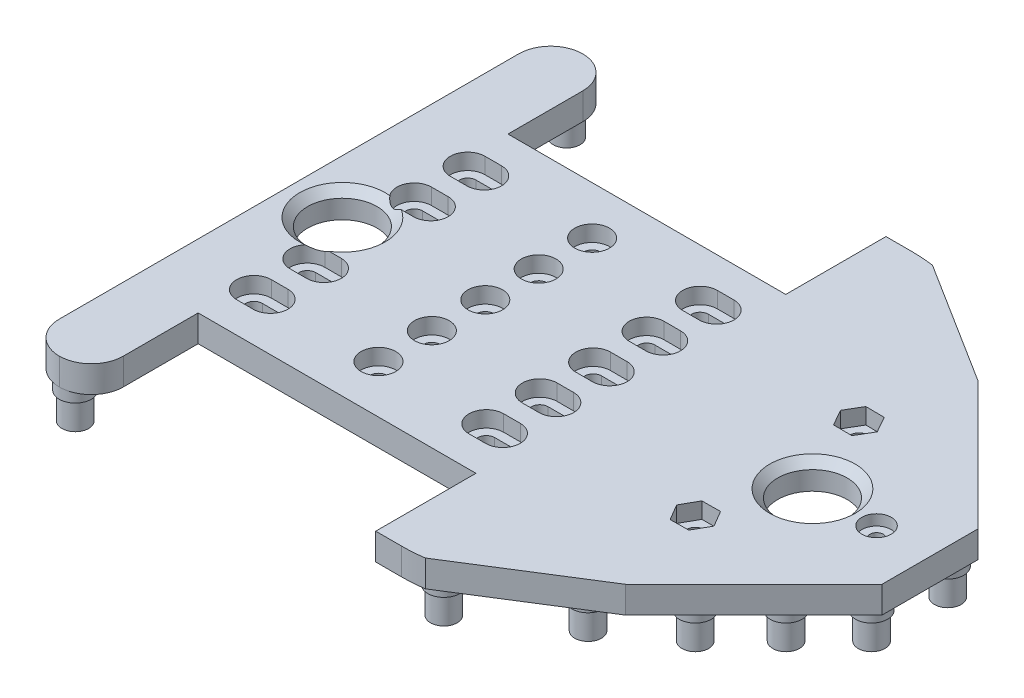
SolidWorks part; units mm, degrees
ref_plane "Front Plane" through (0, 0, 0) normal (0, 0, 1) x (1, 0, 0)
ref_plane "Top Plane" through (0, 0, 0) normal (0, 1, 0) x (1, 0, 0)
ref_plane "Right Plane" through (0, 0, 0) normal (1, 0, 0) x (0, 0, -1)
sketch "Sketch1" plane through (0, 0, 0) normal (0, 1, 0) x (1, 0, 0)
  line L6 (70.2134, 28.8107) -> (31.4419, 67.5821)
  line L47 (70.2134, 19.8215) -> (-33.2366, 19.8215) construction
  line L51 (14.2134, -9.1785) -> (-37.7866, -9.1785)
  line L52 (-37.7866, -9.1785) -> (-37.7866, -29.1785)
  line L53 (-37.7866, -29.1785) -> (-49.7866, -29.1785)
  line L54 (-49.7866, -29.1785) -> (-49.7866, 68.8215)
  line L55 (-49.7866, 68.8215) -> (-37.7866, 68.8215)
  line L56 (-37.7866, 68.8215) -> (-37.7866, 48.8215)
  line L57 (-37.7866, 48.8215) -> (14.2134, 48.8215)
  line L67 (14.2134, 48.8215) -> (14.2134, 67.5821)
  line L68 (14.2134, 67.5821) -> (31.4419, 67.5821)
  line L70 (14.2134, -9.1785) -> (14.2134, -27.9391)
  line L71 (70.2134, 28.8107) -> (70.2134, 10.8324)
  line L72 (14.2134, -27.9391) -> (31.4419, -27.9391)
  line L73 (70.2134, 10.8324) -> (31.4419, -27.9391)
  line L74 (31.4419, 67.5821) -> (31.4419, -27.9391) construction
  line L75 (-36.3366, 39.8215) -> (-33.2366, 39.8215) construction
  line L76 (-36.3366, 41.3715) -> (-33.2366, 41.3715)
  line L77 (-36.3366, 38.2715) -> (-33.2366, 38.2715)
  line L78 (7.1634, 39.8215) -> (10.2634, 39.8215) construction
  line L81 (7.1634, 41.3715) -> (10.2634, 41.3715)
  line L84 (7.1634, 38.2715) -> (10.2634, 38.2715)
  line L87 (7.1634, 29.8215) -> (10.2634, 29.8215) construction
  line L90 (7.1634, 31.3715) -> (10.2634, 31.3715)
  line L93 (7.1634, 28.2715) -> (10.2634, 28.2715)
  line L96 (7.1634, 19.8215) -> (10.2634, 19.8215) construction
  line L99 (7.1634, 21.3715) -> (10.2634, 21.3715)
  line L102 (7.1634, 18.2715) -> (10.2634, 18.2715)
  line L105 (7.1634, 9.8215) -> (10.2634, 9.8215) construction
  line L106 (7.1634, 11.3715) -> (10.2634, 11.3715)
  line L107 (7.1634, 8.2715) -> (10.2634, 8.2715)
  line L108 (7.1634, -0.1785) -> (10.2634, -0.1785) construction
  line L109 (7.1634, 1.3715) -> (10.2634, 1.3715)
  line L110 (7.1634, -1.7285) -> (10.2634, -1.7285)
  line L111 (-36.3366, 29.8215) -> (-33.2366, 29.8215) construction
  line L112 (-36.3366, 31.3715) -> (-33.2366, 31.3715)
  line L113 (-36.3366, 28.2715) -> (-33.2366, 28.2715)
  line L114 (-36.3366, 19.8215) -> (-33.2366, 19.8215) construction
  line L117 (-36.3366, 9.8215) -> (-33.2366, 9.8215) construction
  line L118 (-36.3366, 11.3715) -> (-33.2366, 11.3715)
  line L119 (-36.3366, 8.2715) -> (-33.2366, 8.2715)
  line L120 (-36.3366, -0.1785) -> (-33.2366, -0.1785) construction
  line L121 (-36.3366, 1.3715) -> (-33.2366, 1.3715)
  line L122 (-36.3366, -1.7285) -> (-33.2366, -1.7285)
  line L123 (-34.7866, -0.1785) -> (8.7134, -0.1785) construction
  line L127 (-33.2366, 19.8215) -> (-49.7866, 19.8215) construction
  line L158 (-36.3366, 19.8215) -> (-33.2366, 19.8215) construction
  line L159 (-36.3366, 21.3715) -> (-33.2366, 21.3715) [skipped]
  line L160 (-36.3366, 18.2715) -> (-33.2366, 18.2715) [skipped]
  line L161 (-36.3366, 19.8215) -> (-33.2366, 19.8215) construction
  line L162 (-36.3366, 21.3715) -> (-33.2366, 21.3715) [skipped]
  line L163 (-36.3366, 18.2715) -> (-33.2366, 18.2715) [skipped]
  circle A26 centre (48.2134, 19.8215) radius 6.5
  circle A27 centre (-34.7866, 39.8215) radius 1.55 construction
  arc A44 (-36.3366, 41.3715) -> (-36.3366, 38.2715) centre (-36.3366, 39.8215) ccw
  arc A45 (-33.2366, 38.2715) -> (-33.2366, 41.3715) centre (-33.2366, 39.8215) ccw
  arc A64 (7.1634, 41.3715) -> (7.1634, 38.2715) centre (7.1634, 39.8215) ccw
  arc A65 (10.2634, 38.2715) -> (10.2634, 41.3715) centre (10.2634, 39.8215) ccw
  arc A66 (7.1634, 31.3715) -> (7.1634, 28.2715) centre (7.1634, 29.8215) ccw
  arc A67 (10.2634, 28.2715) -> (10.2634, 31.3715) centre (10.2634, 29.8215) ccw
  arc A68 (7.1634, 21.3715) -> (7.1634, 18.2715) centre (7.1634, 19.8215) ccw
  arc A69 (10.2634, 18.2715) -> (10.2634, 21.3715) centre (10.2634, 19.8215) ccw
  arc A70 (7.1634, 11.3715) -> (7.1634, 8.2715) centre (7.1634, 9.8215) ccw
  arc A71 (10.2634, 8.2715) -> (10.2634, 11.3715) centre (10.2634, 9.8215) ccw
  arc A72 (7.1634, 1.3715) -> (7.1634, -1.7285) centre (7.1634, -0.1785) ccw
  arc A73 (10.2634, -1.7285) -> (10.2634, 1.3715) centre (10.2634, -0.1785) ccw
  arc A74 (-36.3366, 31.3715) -> (-36.3366, 28.2715) centre (-36.3366, 29.8215) ccw
  arc A75 (-33.2366, 28.2715) -> (-33.2366, 31.3715) centre (-33.2366, 29.8215) ccw
  arc A78 (-36.3366, 11.3715) -> (-36.3366, 8.2715) centre (-36.3366, 9.8215) ccw
  arc A79 (-33.2366, 8.2715) -> (-33.2366, 11.3715) centre (-33.2366, 9.8215) ccw
  arc A80 (-36.3366, 1.3715) -> (-36.3366, -1.7285) centre (-36.3366, -0.1785) ccw
  arc A81 (-33.2366, -1.7285) -> (-33.2366, 1.3715) centre (-33.2366, -0.1785) ccw
  circle A82 centre (-13.0366, -0.1785) radius 1.55
  circle A83 centre (-13.0366, 9.8215) radius 1.55
  circle A84 centre (-13.0366, 19.8215) radius 1.55
  circle A85 centre (-13.0366, 29.8215) radius 1.55
  circle A86 centre (-13.0366, 39.8215) radius 1.55
  circle A87 centre (41.5953, 35.1284) radius 1.55
  circle A88 centre (41.5953, 4.5146) radius 1.55
  circle A89 centre (-39.7866, 19.8215) radius 6.5
  circle A91 centre (60.2134, 19.8215) radius 1.25
  arc A114 (-36.3366, 21.3715) -> (-36.3366, 18.2715) centre (-36.3366, 19.8215) ccw [skipped]
  arc A115 (-33.2366, 18.2715) -> (-33.2366, 21.3715) centre (-33.2366, 19.8215) ccw [skipped]
  point P19 (-34.7866, 39.8215)
  point P28 (8.7134, 39.8215)
  point P35 (8.7134, 29.8215)
  point P43 (8.7134, 19.8215)
  point P50 (8.7134, 9.8215)
  point P57 (8.7134, -0.1785)
  point P64 (-34.7866, 29.8215)
  point P71 (-34.7866, 19.8215)
  point P80 (-34.7866, 9.8215)
  point P88 (-34.7866, -0.1785)
  point P110 (-34.7866, 19.8215)
  point P122 (-34.7866, 19.8215)
  point P129 (-34.7866, 19.8215)
  point P136 (-34.7866, 19.8215)
  point P143 (-34.7866, 19.8215)
  point P150 (-34.7866, 19.8215)
  point P157 (-34.7866, 19.8215)
  point P164 (-34.7866, 19.8215)
  point P171 (-34.7866, 19.8215)
  point P178 (-34.7866, 19.8215)
  point P185 (-34.7866, 19.8215)
  point P192 (-34.7866, 19.8215)
  point P199 (-34.7866, 19.8215)
  dimension "D11" = 20
  dimension "D10" = 20
  dimension "D15" = 13
  dimension "D8" = 135
  dimension "D9" = 12
  dimension "D17" = 1.55
  dimension "D13" = 3.1
  dimension "D14" = 15
  dimension "D16" = 9
  dimension "D18" = 5
  dimension "D19" = 3.1
  dimension "D20" = 5
  dimension "D21" = 3.1
  dimension "D24" = 13
  dimension "D26" = 2.5
  dimension "D2" = 58
  dimension "D3" = 17.9783
  dimension "D4" = 64
  dimension "D5" = 120
  dimension "D6" = 22
  dimension "D7" = 12
  dimension "D25" = 10
  dimension "D27" = 10
  dimension "D28" = 17.2286
  dimension "D12" = 18.7606
extrude "Boss-Extrude1" add sketch "Sketch1" along normal blind 5
fillet "Fillet1" radius 30 2 edges at (31.4419, 2.5, 27.9391) (31.4419, 2.5, -67.5821)
fillet "Fillet2" radius 6 4 edges at (-37.7866, 2.5, 29.1785) (-49.7866, 2.5, 29.1785) (-37.7866, 2.5, -68.8215) (-49.7866, 2.5, -68.8215)
sketch "Sketch3" plane through (0, 5, 0) normal (0, 1, 0) x (1, 0, 0)
  line L0 (-33.2366, 39.8215) -> (-36.3366, 39.8215) construction
  line L1 (-33.2366, 36.5715) -> (-36.3366, 36.5715)
  line L2 (-33.2366, 43.0715) -> (-36.3366, 43.0715)
  line L3 (10.2634, 39.8215) -> (7.1634, 39.8215) construction
  line L4 (10.2634, 36.5715) -> (7.1634, 36.5715)
  line L5 (10.2634, 43.0715) -> (7.1634, 43.0715)
  line L6 (10.2634, 29.8215) -> (7.1634, 29.8215) construction
  line L7 (10.2634, 26.5715) -> (7.1634, 26.5715)
  line L8 (10.2634, 33.0715) -> (7.1634, 33.0715)
  line L9 (10.2634, 19.8215) -> (7.1634, 19.8215) construction
  line L10 (10.2634, 16.5715) -> (7.1634, 16.5715)
  line L11 (10.2634, 23.0715) -> (7.1634, 23.0715)
  line L12 (10.2634, 9.8215) -> (7.1634, 9.8215) construction
  line L13 (10.2634, 6.5715) -> (7.1634, 6.5715)
  line L14 (10.2634, 13.0715) -> (7.1634, 13.0715)
  line L15 (10.2634, -0.1785) -> (7.1634, -0.1785) construction
  line L16 (10.2634, -3.4285) -> (7.1634, -3.4285)
  line L17 (10.2634, 3.0715) -> (7.1634, 3.0715)
  line L18 (-33.2366, 29.8215) -> (-36.3366, 29.8215) construction
  line L19 (-33.2366, 26.5715) -> (-36.3366, 26.5715)
  line L20 (-33.2366, 33.0715) -> (-36.3366, 33.0715)
  line L21 (70.2134, 19.8215) -> (39.7181, 19.8215) construction
  line L24 (-33.2366, 9.8215) -> (-36.3366, 9.8215) construction
  line L25 (-33.2366, 6.5715) -> (-36.3366, 6.5715)
  line L26 (-33.2366, 13.0715) -> (-36.3366, 13.0715)
  line L27 (-33.2366, -0.1785) -> (-36.3366, -0.1785) construction
  line L28 (-33.2366, -3.4285) -> (-36.3366, -3.4285)
  line L29 (-33.2366, 3.0715) -> (-36.3366, 3.0715)
  line L31 (43.3551, 38.1122) -> (39.8912, 38.1443)
  line L32 (39.8912, 38.1443) -> (38.1313, 35.1606)
  line L33 (38.1313, 35.1606) -> (39.8354, 32.1446)
  line L34 (39.8354, 32.1446) -> (43.2994, 32.1124)
  line L35 (43.2994, 32.1124) -> (45.0592, 35.0962)
  line L36 (45.0592, 35.0962) -> (43.3551, 38.1122)
  line L42 (70.2134, 28.8107) -> (70.2134, 10.8324) construction
  line L43 (45.0592, 4.5468) -> (43.3551, 1.5309)
  line L44 (43.2994, 7.5306) -> (45.0592, 4.5468)
  line L45 (39.8354, 7.4984) -> (43.2994, 7.5306)
  line L46 (38.1313, 4.4825) -> (39.8354, 7.4984)
  line L47 (39.8912, 1.4987) -> (38.1313, 4.4825)
  line L48 (43.3551, 1.5309) -> (39.8912, 1.4987)
  line L87 (-33.2366, 19.8215) -> (-36.3366, 19.8215) construction
  line L88 (-33.2366, 16.5715) -> (-36.3366, 16.5715) [skipped]
  line L89 (-33.2366, 23.0715) -> (-36.3366, 23.0715) [skipped]
  line L90 (-33.2366, 19.8215) -> (-36.3366, 19.8215) construction
  line L91 (-33.2366, 16.5715) -> (-36.3366, 16.5715) [skipped]
  line L92 (-33.2366, 23.0715) -> (-36.3366, 23.0715) [skipped]
  arc A0 (-33.2366, 36.5715) -> (-33.2366, 43.0715) centre (-33.2366, 39.8215) ccw
  arc A1 (-36.3366, 43.0715) -> (-36.3366, 36.5715) centre (-36.3366, 39.8215) ccw
  arc A2 (10.2634, 36.5715) -> (10.2634, 43.0715) centre (10.2634, 39.8215) ccw
  arc A3 (7.1634, 43.0715) -> (7.1634, 36.5715) centre (7.1634, 39.8215) ccw
  arc A4 (10.2634, 26.5715) -> (10.2634, 33.0715) centre (10.2634, 29.8215) ccw
  arc A5 (7.1634, 33.0715) -> (7.1634, 26.5715) centre (7.1634, 29.8215) ccw
  arc A6 (10.2634, 16.5715) -> (10.2634, 23.0715) centre (10.2634, 19.8215) ccw
  arc A7 (7.1634, 23.0715) -> (7.1634, 16.5715) centre (7.1634, 19.8215) ccw
  arc A8 (10.2634, 6.5715) -> (10.2634, 13.0715) centre (10.2634, 9.8215) ccw
  arc A9 (7.1634, 13.0715) -> (7.1634, 6.5715) centre (7.1634, 9.8215) ccw
  arc A10 (10.2634, -3.4285) -> (10.2634, 3.0715) centre (10.2634, -0.1785) ccw
  arc A11 (7.1634, 3.0715) -> (7.1634, -3.4285) centre (7.1634, -0.1785) ccw
  arc A12 (-33.2366, 26.5715) -> (-33.2366, 33.0715) centre (-33.2366, 29.8215) ccw
  arc A13 (-36.3366, 33.0715) -> (-36.3366, 26.5715) centre (-36.3366, 29.8215) ccw
  arc A16 (-33.2366, 6.5715) -> (-33.2366, 13.0715) centre (-33.2366, 9.8215) ccw
  arc A17 (-36.3366, 13.0715) -> (-36.3366, 6.5715) centre (-36.3366, 9.8215) ccw
  arc A18 (-33.2366, -3.4285) -> (-33.2366, 3.0715) centre (-33.2366, -0.1785) ccw
  arc A19 (-36.3366, 3.0715) -> (-36.3366, -3.4285) centre (-36.3366, -0.1785) ccw
  circle A20 centre (-13.0366, 39.8215) radius 3.25
  circle A21 centre (-13.0366, 29.8215) radius 3.25
  circle A22 centre (-13.0366, 19.8215) radius 3.25
  circle A23 centre (-13.0366, 9.8215) radius 3.25
  circle A24 centre (-13.0366, -0.1785) radius 3.25
  circle A27 centre (41.5953, 35.1284) radius 3 construction
  arc A60 (-33.2366, 16.5715) -> (-33.2366, 23.0715) centre (-33.2366, 19.8215) ccw [skipped]
  arc A61 (-36.3366, 23.0715) -> (-36.3366, 16.5715) centre (-36.3366, 19.8215) ccw [skipped]
  point P4 (-34.7866, 39.8215)
  point P14 (8.7134, 39.8215)
  point P21 (8.7134, 29.8215)
  point P28 (8.7134, 19.8215)
  point P35 (8.7134, 9.8215)
  point P42 (8.7134, -0.1785)
  point P49 (-34.7866, 29.8215)
  point P63 (-34.7866, 9.8215)
  point P70 (-34.7866, -0.1785)
  point P101 (-34.7866, 19.8215)
  point P108 (-34.7866, 19.8215)
  point P115 (-34.7866, 19.8215)
  point P122 (-34.7866, 19.8215)
  point P129 (-34.7866, 19.8215)
  point P136 (-34.7866, 19.8215)
  point P143 (-34.7866, 19.8215)
  point P150 (-34.7866, 19.8215)
  point P157 (-34.7866, 19.8215)
  point P164 (-34.7866, 19.8215)
  point P171 (-34.7866, 19.8215)
  point P178 (-34.7866, 19.8215)
  point P185 (-34.7866, 19.8215)
  point P192 (-34.7866, 19.8215)
  point P199 (-34.7866, 19.8215)
  point P206 (-34.7866, 19.8215)
  point P213 (-34.7866, 19.8215)
  dimension "D1" = 3.25
  dimension "D3" = 6.5
  dimension "D5" = 6
  dimension "D6" = 6
  dimension "D2" = 5
  dimension "D4" = 5
extrude "Cut-Extrude2" cut sketch "Sketch3" against normal blind 3
sketch "Sketch4" plane through (0, 0, 0) normal (0, -1, 0) x (-1, 0, 0)
  line L0 (-70.2134, 19.8215) -> (49.7866, 19.8215) construction
  line L1 (-70.2134, 28.8107) -> (-70.2134, 10.8324) construction
  line L2 (49.7866, -23.1785) -> (49.7866, 62.8215) construction
  line L3 (-14.2134, -9.1785) -> (-14.2134, -27.9391) construction
  line L4 (-14.2134, -9.1785) -> (37.7866, -9.1785) construction
  line L5 (43.7866, -29.1785) -> (43.7866, 68.8215) construction
  line L7 (-70.2134, 10.8324) -> (-40.2287, -19.1523) construction
  circle A0 centre (-22.2134, -23.1785) radius 3
  circle A1 centre (-38.2134, -12.1785) radius 3
  circle A2 centre (-22.2134, -23.1785) radius 8 construction
  circle A3 centre (-38.2134, -12.1785) radius 8 construction
  circle A4 centre (-49.9134, 43.4538) radius 5 construction
  circle A5 centre (-66.4134, 26.9538) radius 5 construction
  circle A8 centre (43.7866, -26.1785) radius 3
  circle A9 centre (43.7866, -26.1785) radius 5 construction
  circle A10 centre (43.7866, 65.8215) radius 5 construction
  circle A11 centre (43.7866, 65.8215) radius 3
  circle A18 centre (-58.4134, 34.9538) radius 5 construction
  circle A19 centre (-38.2134, 51.8215) radius 8 construction
  circle A20 centre (-22.2134, 62.8215) radius 8 construction
  circle A24 centre (-58.4134, 4.6892) radius 5 construction
  circle A25 centre (-58.4134, 4.6892) radius 3
  circle A26 centre (-49.9134, -3.8108) radius 3
  circle A27 centre (-66.4134, 12.6892) radius 3
  circle A28 centre (-66.4134, 12.6892) radius 5 construction
  circle A29 centre (-49.9134, -3.8108) radius 5 construction
  circle A30 centre (-66.4134, 26.9538) radius 3
  circle A31 centre (-49.9134, 43.4538) radius 3
  circle A32 centre (-58.4134, 34.9538) radius 3
  circle A33 centre (-38.2134, 51.8215) radius 3
  circle A34 centre (-22.2134, 62.8215) radius 3
  dimension "D1" = 6
  dimension "D2" = 8
  dimension "D4" = 16
  dimension "D5" = 24
  dimension "D6" = 3
  dimension "D7" = 6
  dimension "D8" = 6
  dimension "D9" = 10
  dimension "D11" = 10
  dimension "D16" = 6
  dimension "D17" = 6
  dimension "D18" = 4
  dimension "D3" = 14
  dimension "D10" = 46
  dimension "D12" = 8
  dimension "D13" = 16.5
  dimension "D14" = 3.8
  dimension "D15" = 4
  dimension "D19" = 4
extrude "Boss-Extrude2" add sketch "Sketch4" along normal blind 2
sketch "Sketch5" plane through (0, -2, 0) normal (0, -1, 0) x (-1, 0, 0)
  line L0 (-70.2134, 19.8215) -> (49.7866, 19.8215) construction
  line L1 (-70.2134, 28.8107) -> (-70.2134, 10.8324) construction
  line L2 (49.7866, -23.1785) -> (49.7866, 62.8215) construction
  circle A0 centre (-22.2134, -23.1785) radius 2.5
  circle A5 centre (43.7866, -26.1785) radius 2.5
  circle A12 centre (-38.2134, -12.1785) radius 2.5
  circle A13 centre (-49.9134, -3.8108) radius 2.5
  circle A14 centre (-58.4134, 4.6892) radius 2.5
  circle A15 centre (-66.4134, 12.6892) radius 2.5
  circle A16 centre (-66.4134, 26.9538) radius 2.5
  circle A17 centre (-58.4134, 34.9538) radius 2.5
  circle A18 centre (-49.9134, 43.4538) radius 2.5
  circle A19 centre (-38.2134, 51.8215) radius 2.5
  circle A20 centre (43.7866, 65.8215) radius 2.5
  circle A21 centre (-22.2134, 62.8215) radius 2.5
  dimension "D1" = 5
  dimension "D2" = 5
extrude "Boss-Extrude3" add sketch "Sketch5" along normal blind 5
sketch "Sketch6" plane through (0, 5, 0) normal (0, 1, 0) x (1, 0, 0)
  line L0 (23.2134, -27.6439) -> (46.2134, -13.1676)
  line L2 (70.2134, 19.8215) -> (-49.7866, 19.8215) construction
  line L3 (70.2134, 28.8107) -> (70.2134, 10.8324) construction
  line L4 (-49.7866, -23.1785) -> (-49.7866, 62.8215) construction
  line L6 (70.2134, 10.8324) -> (40.2287, -19.1523) construction
  line L7 (14.2134, -9.1785) -> (14.2134, -27.9391) construction
  line L8 (23.2134, -27.6439) -> (46.2134, -27.6439)
  line L9 (46.2134, -27.6439) -> (46.2134, -13.1676)
  line L10 (46.2134, 67.2869) -> (46.2134, 52.8107)
  line L11 (23.2134, 67.2869) -> (46.2134, 67.2869)
  line L12 (23.2134, 67.2869) -> (46.2134, 52.8107)
  arc A0 (19.0155, -27.9391) -> (40.2287, -19.1523) centre (19.0155, 2.0609) ccw construction
  dimension "D1" = 9
  dimension "D2" = 24
extrude "Cut-Extrude3" cut sketch "Sketch6" against normal through all
sketch "Sketch7" plane through (0, 5, 0) normal (0, 1, 0) x (1, 0, 0)
  circle A0 centre (60.2134, 19.8215) radius 2.75
  dimension "D1" = 5.5
extrude "Cut-Extrude4" cut sketch "Sketch7" against normal blind 2
chamfer "Chamfer1" distance 1.5 2 edges at (48.2134, 5, -13.3215) (-39.7866, 5, -13.3215)
